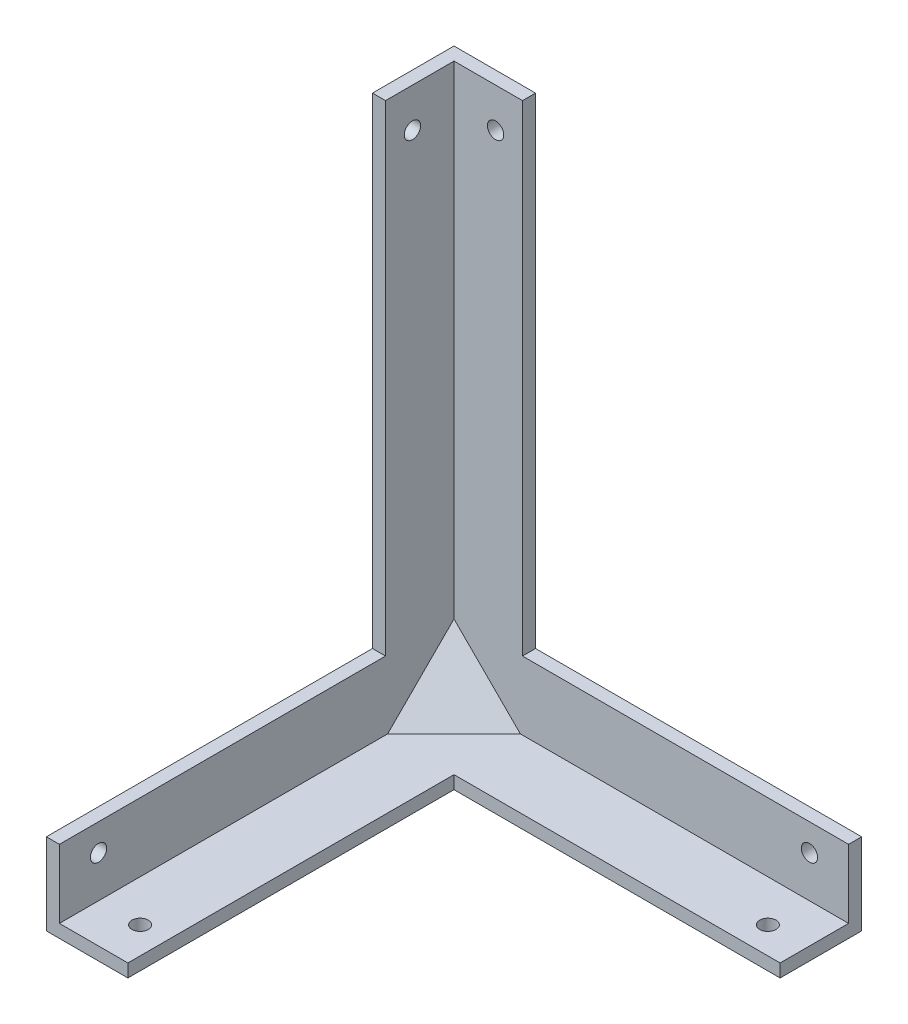
SolidWorks part; units mm, degrees
ref_plane "前视基准面" through (0, 0, 0) normal (0, 0, 1) x (1, 0, 0)
ref_plane "上视基准面" through (0, 0, 0) normal (0, 1, 0) x (1, 0, 0)
ref_plane "右视基准面" through (0, 0, 0) normal (1, 0, 0) x (0, 0, -1)
sketch "草图1" plane through (0, 0, 0) normal (0, 0, 1) x (1, 0, 0)
  line L0 (0, 25) -> (0, 0)
  line L1 (0, 0) -> (25, 0)
  line L2 (25, 0) -> (25, 4)
  line L3 (25, 4) -> (4, 4)
  line L4 (4, 4) -> (4, 25)
  line L5 (4, 25) -> (0, 25)
  dimension "D1" = 25
  dimension "D2" = 4
extrude "凸台-拉伸1" add sketch "草图1" along normal blind 125
sketch "草图2" plane through (0, 0, 0) normal (-1, 0, 0) x (0, 0, 1)
  line L1 (0, 0) -> (0, 25)
  line L2 (0, 0) -> (0, 4) construction
  line L3 (0, 0) -> (0, 4) construction
  line L4 (0, 25) -> (4, 25)
  line L5 (125, 25) -> (0, 25) construction
  line L6 (4, 25) -> (4, 4)
  line L7 (4, 4) -> (25, 4)
  line L8 (25, 4) -> (25, 0)
  line L9 (125, 0) -> (0, 0) construction
  line L10 (25, 0) -> (0, 0)
extrude "凸台-拉伸2" add sketch "草图2" against normal blind 125
sketch "草图3" plane through (0, 0, 0) normal (0, -1, 0) x (1, 0, 0)
  line L0 (4, 125) -> (0, 125) construction
  line L1 (4, 125) -> (0, 125) construction
  line L2 (0, 25) -> (0, 0)
  line L3 (0, 125) -> (0, 0) construction
  line L4 (0, 0) -> (25, 0)
  line L5 (0, 0) -> (125, 0) construction
  line L6 (25, 0) -> (25, 4)
  line L7 (25, 4) -> (4, 4)
  line L8 (4, 4) -> (4, 25)
  line L9 (4, 25) -> (0, 25)
  line L10 (125, 0) -> (125, 25) construction
extrude "凸台-拉伸3" add sketch "草图3" against normal blind 172.5
hole_wizard "M6 螺纹孔1" positions "草图4" profile "草图5" tap size "M6" standard "GB" end condition through all
sketch "草图4" plane through (0, 4, 0) normal (0, 1, 0) x (1, 0, 0)
  line L0 (125, -25) -> (25, -25) construction
  line L1 (25, -125) -> (25, -25) construction
  line L2 (25, -125) -> (4, -125) construction
  line L3 (125, -25) -> (125, -4) construction
  point P0 (113, -16.75)
  point P2 (16.75, -113)
  dimension "D1" = 8.25
  dimension "D2" = 8.25
  dimension "D3" = 12
  dimension "D4" = 12
sketch "草图5" plane through (113, 4, 16.75) normal (1, 0, 0) x (0, 0, 1)
  line L0 (0, 0) -> (0, 4)
  line L1 (0, 4) -> (2.5, 4)
  line L2 (2.5, 4) -> (2.5, 0)
  line L5 (2.5, 0) -> (0, 0)
  line L11 (0, -6.35) -> (0, 107.95) construction
  dimension "通孔螺纹孔钻头直径" = 5
  dimension "通孔螺纹孔钻头深度" = 4
hole_wizard "M6 螺纹孔2" positions "草图6" profile "草图7" tap size "M6" standard "GB" end condition through all
sketch "草图6" plane through (4, 0, 0) normal (1, 0, 0) x (0, 0, -1)
  line L0 (-125, 25) -> (-25, 25) construction
  line L1 (-25, 172.5) -> (-25, 25) construction
  line L2 (-125, 4) -> (-125, 25) construction
  line L3 (-4, 172.5) -> (-25, 172.5) construction
  point P0 (-113, 16.75)
  point P2 (-16.75, 160.5)
  dimension "D1" = 8.25
  dimension "D2" = 8.25
  dimension "D3" = 12
  dimension "D4" = 12
sketch "草图7" plane through (4, 16.75, 113) normal (0, 1, 0) x (0, 0, -1)
  line L0 (0, 0) -> (0, 4)
  line L1 (0, 4) -> (2.5, 4)
  line L2 (2.5, 4) -> (2.5, 0)
  line L5 (2.5, 0) -> (0, 0)
  line L11 (0, -6.35) -> (0, 107.95) construction
  dimension "通孔螺纹孔钻头直径" = 5
  dimension "通孔螺纹孔钻头深度" = 4
hole_wizard "M6 螺纹孔3" positions "草图8" profile "草图9" tap size "M6" standard "GB" end condition through all
sketch "草图8" plane through (0, 0, 4) normal (0, 0, 1) x (1, 0, 0)
  line L0 (25, 172.5) -> (25, 25) construction
  line L1 (25, 172.5) -> (4, 172.5) construction
  line L2 (125, 25) -> (25, 25) construction
  line L3 (125, 4) -> (125, 25) construction
  point P0 (16.75, 160.5)
  point P2 (113, 16.75)
  dimension "D1" = 8.25
  dimension "D2" = 12
  dimension "D3" = 8.25
  dimension "D4" = 12
sketch "草图9" plane through (16.75, 160.5, 4) normal (1, 0, 0) x (0, -1, 0)
  line L0 (0, 0) -> (0, 4)
  line L1 (0, 4) -> (2.5, 4)
  line L2 (2.5, 4) -> (2.5, 0)
  line L5 (2.5, 0) -> (0, 0)
  line L11 (0, -6.35) -> (0, 107.95) construction
  dimension "通孔螺纹孔钻头直径" = 5
  dimension "通孔螺纹孔钻头深度" = 4
ref_plane "基准面1" through (18, 18, 18) normal (0.5774, 0.5774, 0.5774) x (0.8165, -0.4082, -0.4082)
ref_plane "基准面2" through (10.7831, 10.7831, 10.7831) normal (0.5774, 0.5774, 0.5774) x (0.8165, -0.4082, -0.4082)
ref_axis "基准轴1" through (4, 24.3494, 4) along (0, -0.7071, 0.7071)
sketch "草图10" plane through (10.7831, 10.7831, 10.7831) normal (0.5774, 0.5774, 0.5774) x (0.8165, -0.4082, -0.4082)
  line L0 (-49.398, -85.5599) -> (0, 0) construction
  line L1 (98.7961, 0) -> (0, 0) construction
  line L2 (0, 0) -> (-68.7898, 119.1475) construction
  line L3 (-49.398, -85.5599) -> (0, 0)
  line L4 (98.7961, 0) -> (0, 0)
  line L5 (0, 0) -> (-68.7898, 119.1475)
  line L6 (90.2229, 14.8492) -> (8.5732, 14.8492)
  line L7 (8.5732, 14.8492) -> (-51.6434, 119.1475)
  line L8 (-51.6434, 119.1475) -> (-68.7898, 119.1475)
  line L9 (-68.7898, 119.1475) -> (0, 0)
  line L10 (0, 0) -> (98.7961, 0)
  line L11 (98.7961, 0) -> (90.2229, 14.8492)
  line L14 (-51.6434, 119.1475) -> (-68.7898, 119.1475)
  line L18 (-8.3076, 14.3892) -> (-8.3076, -14.3892)
  line L19 (-8.3076, 14.3892) -> (-8.3076, -14.3892) construction
  line L20 (-8.3076, -14.3892) -> (16.6152, 0)
  line L21 (16.6152, 0) -> (-8.3076, 14.3892)
  dimension "D1" = 0
extrude "凸台-拉伸4" add sketch "草图10" against normal blind 40 draft 27 contours L3 L20 L4 | L5 L18 L3 | L4 L21 L5 region at (6.261, 13.0442, 13.0442) region at (13.0442, 6.261, 13.0442) region at (13.0442, 13.0442, 6.261)
